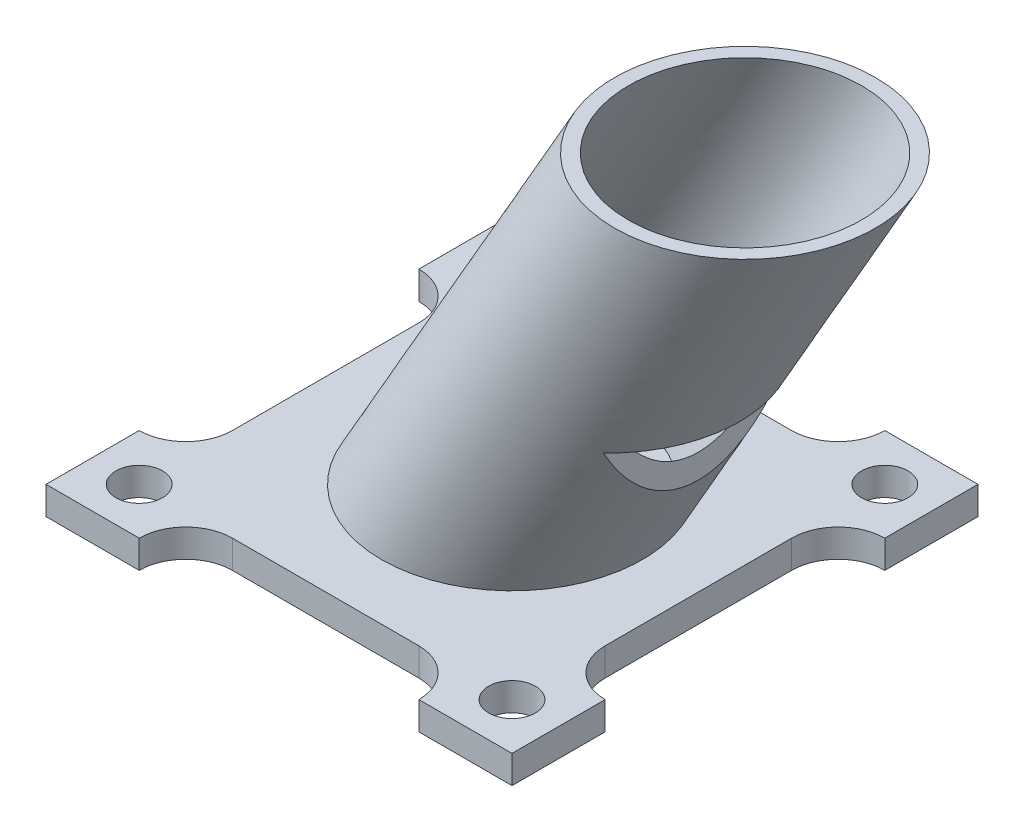
SolidWorks part; units mm, degrees
ref_plane "Front Plane" through (0, 0, 0) normal (0, 0, 1) x (1, 0, 0)
ref_plane "Top Plane" through (0, 0, 0) normal (0, 1, 0) x (1, 0, 0)
ref_plane "Right Plane" through (0, 0, 0) normal (1, 0, 0) x (0, 0, -1)
sketch "Sketch1" plane through (0, 0, 0) normal (0, 1, 0) x (1, 0, 0)
  line L1 (-25, 25) -> (25, 25)
  line L2 (-25, 25) -> (-25, -25)
  line L3 (-25, -25) -> (25, -25)
  line L4 (25, 25) -> (25, -25)
  line L5 (-25, 25) -> (25, -25) construction
  line L6 (-25, -25) -> (25, 25) construction
  point P0 (0, 0)
  dimension "D1" = 50
  dimension "D2" = 50
extrude "Boss-Extrude1" add sketch "Sketch1" along normal blind 3
sketch "Sketch2" plane through (0, 0, 0) normal (0, 0, 1) x (1, 0, 0)
  line L0 (0, 3) -> (25, 46.3013)
  line L1 (0, -1.65) -> (0, 1.65) construction
  line L2 (-25, 3) -> (25, 3) construction
  dimension "D1" = 60
  dimension "D2" = 50
sketch "Sketch3" plane through (0, 3, 0) normal (0, 1, 0) x (1, 0, 0)
  circle A0 centre (0, 0) radius 14
  circle A1 centre (0, 0) radius 12.5
  dimension "D1" = 28
  dimension "D2" = 25
sweep "Sweep1" add profiles "Sketch3" path "Sketch2"
sketch "Sketch4" plane through (0, 0, 0) normal (0, 1, 0) x (1, 0, 0)
  line L0 (-25.4657, 0) -> (25.4657, 0) construction
  line L1 (0, -25.4657) -> (0, 25.4657) construction
  circle A0 centre (-20, 20) radius 2.5
  circle A1 centre (20, 20) radius 2.5
  dimension "D1" = 5
  dimension "D2" = 20
  dimension "D3" = 20
  dimension "D4" = 20
  dimension "D5" = 20
sketch "Sketch5" plane through (0, 0, 0) normal (0, 1, 0) x (1, 0, 0)
extrude "Cut-Extrude13" cut sketch "Sketch4" along normal blind 3 contours A0
sketch "Sketch8" plane through (0, 0, 0) normal (0, 1, 0) x (1, 0, 0)
  line L0 (-25.4657, 0) -> (25.4657, 0) construction
  line L1 (0, -25.4657) -> (0, 25.4657) construction
  circle A0 centre (20, 20) radius 2.5
  dimension "D1" = 5
  dimension "D2" = 20
  dimension "D3" = 20
extrude "Cut-Extrude20" cut sketch "Sketch8" along normal blind 3
mirror "Mirror1" about plane through (0, 0, 0) normal (0, 0, 1) of "Cut-Extrude20"
mirror "Mirror2" about plane through (0, 0, 0) normal (0, 0, 1) of "Cut-Extrude13"
sketch "Sketch9" plane through (0, 0, 0) normal (0, 1, 0) x (1, 0, 0)
  line L0 (-10, 25) -> (10, 25) construction
  line L1 (25, 25) -> (-25, 25) construction
  line L2 (-10, 30) -> (10, 30)
  line L3 (-10, 20) -> (10, 20)
  line L4 (0, -25.4657) -> (0, 25.4657) construction
  arc A0 (-10, 30) -> (-10, 20) centre (-10, 25) ccw
  arc A1 (10, 20) -> (10, 30) centre (10, 25) ccw
  point P4 (0, 25)
  dimension "D1" = 10
  dimension "D2" = 10
  dimension "D3" = 5
  dimension "D4" = 5
extrude "Cut-Extrude22" cut sketch "Sketch9" along normal blind 21
ref_axis "Axis4" through (0, 17.0534, 0) along (0, 1, 0)
pattern_circular "CirPattern4" count 4 over 360 about axis through (0, 17.0534, 0) along (0, 1, 0) of "Cut-Extrude22"
